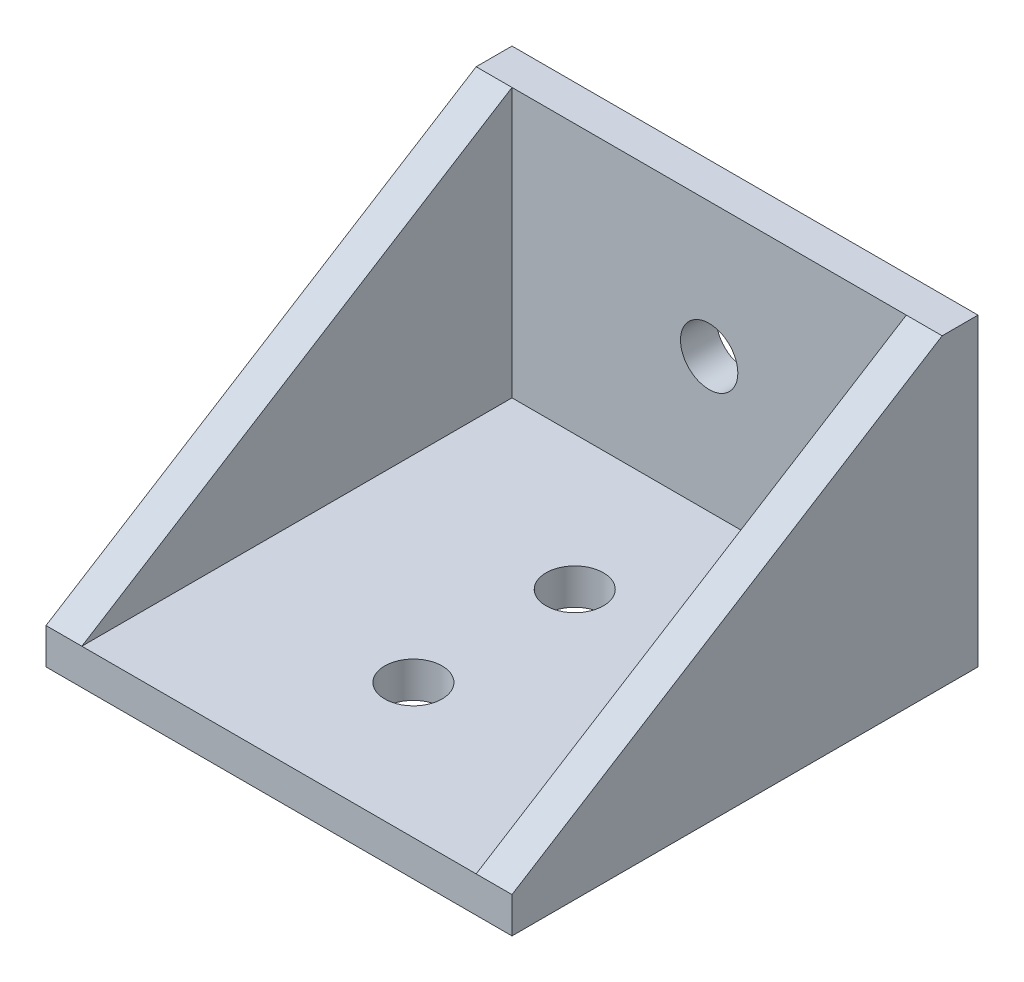
SolidWorks part; units mm, degrees
ref_plane "正面" through (0, 0, 0) normal (0, 0, 1) x (1, 0, 0)
ref_plane "平面" through (0, 0, 0) normal (0, 1, 0) x (1, 0, 0)
ref_plane "右側面" through (0, 0, 0) normal (1, 0, 0) x (0, 0, -1)
sketch "ｽｹｯﾁ1" plane through (0, 0, 0) normal (0, 1, 0) x (1, 0, 0)
  line L1 (-13, -13) -> (13, -13)
  line L2 (-13, -13) -> (-13, 13)
  line L3 (-13, 13) -> (13, 13)
  line L4 (13, -13) -> (13, 13)
  line L5 (-13, -13) -> (13, 13) construction
  line L6 (-13, 13) -> (13, -13) construction
  point P0 (0, 0)
  dimension "D1" = 26
extrude "ﾎﾞｽ - 押し出し1" add sketch "ｽｹｯﾁ1" along normal blind 17
sketch "ｽｹｯﾁ2" plane through (13, 0, 0) normal (1, 0, 0) x (0, 0, -1)
  line L0 (11, 17) -> (-13, 2)
  line L1 (-13, 17) -> (13, 17) construction
  line L2 (-13, 17) -> (-13, 0) construction
  line L3 (-13, 2) -> (-13, 17)
  line L4 (-13, 17) -> (11, 17)
  dimension "D1" = 2
  dimension "D2" = 2
extrude "ｶｯﾄ - 押し出し1" cut sketch "ｽｹｯﾁ2" against normal through all
shell "ｼｪﾙ2" thickness 2 removed face at (0, 1, 13) removed face at (0, 17, -12) removed face at (0, 9.5, 1)
sketch "ｽｹｯﾁ3" plane through (0, 2, 0) normal (0, 1, 0) x (1, 0, 0)
  line L0 (-11, 11) -> (11, 11) construction
  line L1 (-11, -13) -> (11, -13) construction
  circle A0 centre (0, 3.5) radius 1.6
  circle A1 centre (0, -5.5) radius 1.6
  point P4 (0, 0)
  dimension "D1" = 3.2
  dimension "D2" = 7.5
  dimension "D3" = 7.5
extrude "ｶｯﾄ - 押し出し2" cut sketch "ｽｹｯﾁ3" against normal through all
sketch "ｽｹｯﾁ4" plane through (0, 0, -11) normal (0, 0, 1) x (1, 0, 0)
  line L0 (11, 2) -> (-11, 2) construction
  circle A0 centre (0, 9.5) radius 1.6
  point P2 (0, 0)
  point P5 (0, 2)
  dimension "D1" = 3.2
  dimension "D2" = 7.5
extrude "ｶｯﾄ - 押し出し3" cut sketch "ｽｹｯﾁ4" against normal through all
